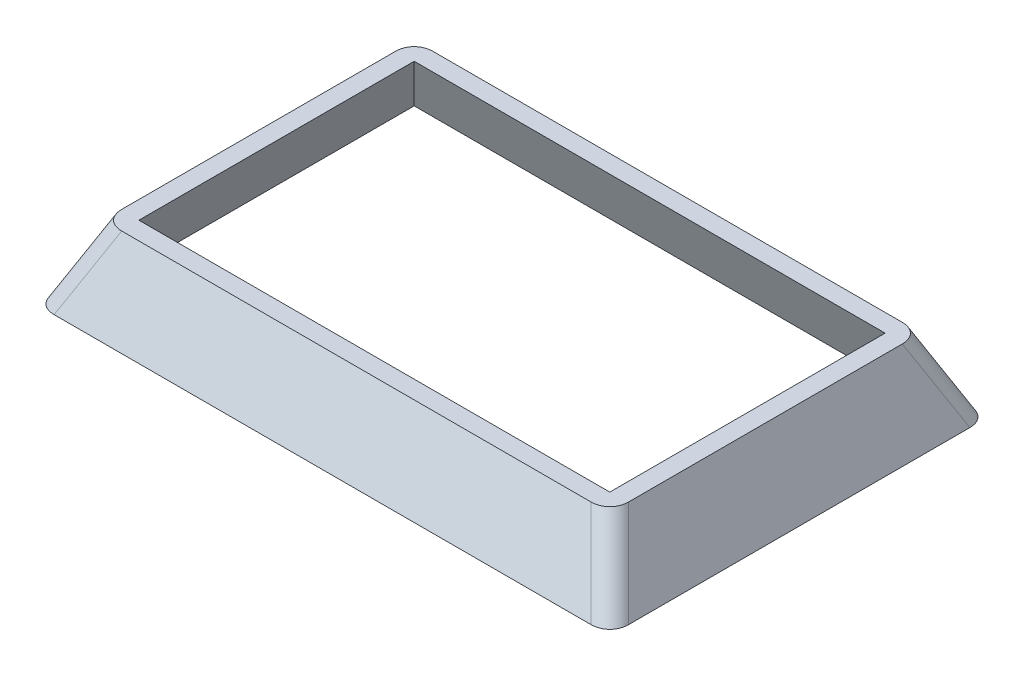
SolidWorks part; units mm, degrees
ref_plane "Plan de face" through (0, 0, 0) normal (0, 0, 1) x (1, 0, 0)
ref_plane "Plan de dessus" through (0, 0, 0) normal (0, 1, 0) x (1, 0, 0)
ref_plane "Plan de droite" through (0, 0, 0) normal (1, 0, 0) x (0, 0, -1)
sketch "Esquisse2" plane through (0, 0, 0) normal (0, 1, 0) x (1, 0, 0)
  line L0 (-22.75, 13.3) -> (22.75, 13.3)
  line L1 (-22.75, 13.3) -> (-22.75, -13.3)
  line L2 (-22.75, -13.3) -> (22.75, -13.3)
  line L3 (22.75, 13.3) -> (22.75, -13.3)
  line L4 (-22.75, 13.3) -> (22.75, -13.3) construction
  line L9 (-27.75, 18.3) -> (27.75, 18.3)
  line L10 (27.75, 18.3) -> (27.75, -18.3)
  line L11 (-27.75, -18.3) -> (27.75, -18.3)
  line L12 (-27.75, 18.3) -> (-27.75, -18.3)
  point P9 (0, 0)
  dimension "D1" = 45.5
  dimension "D2" = 26.6
  dimension "D3" = 5
extrude "Boss.-Extru.1" add sketch "Esquisse2" along normal blind 7
chamfer "Chanfrein1" distance 7 angle 25 8 edges at (0, 7, 18.3) (27.75, 7, 0) (0, 7, -18.3) (-27.75, 7, 0) (0, 0, 13.3) (-22.75, 0, 0) (0, 0, -13.3) (22.75, 0, 0) first distance on face at (0, 3.5, 18.3) first distance on face at (27.75, 3.5, 0) first distance on face at (0, 3.5, -18.3) first distance on face at (-27.75, 3.5, 0) first distance on face at (0, 3.5, 13.3) first distance on face at (-22.75, 3.5, 0) first distance on face at (0, 3.5, -13.3) first distance on face at (22.75, 3.5, 0)
fillet "Congé3" radius 2 4 edges at (26.1179, 3.5, -16.6679) (-26.1179, 3.5, -16.6679) (-26.1179, 3.5, 16.6679) (26.1179, 3.5, 16.6679)
